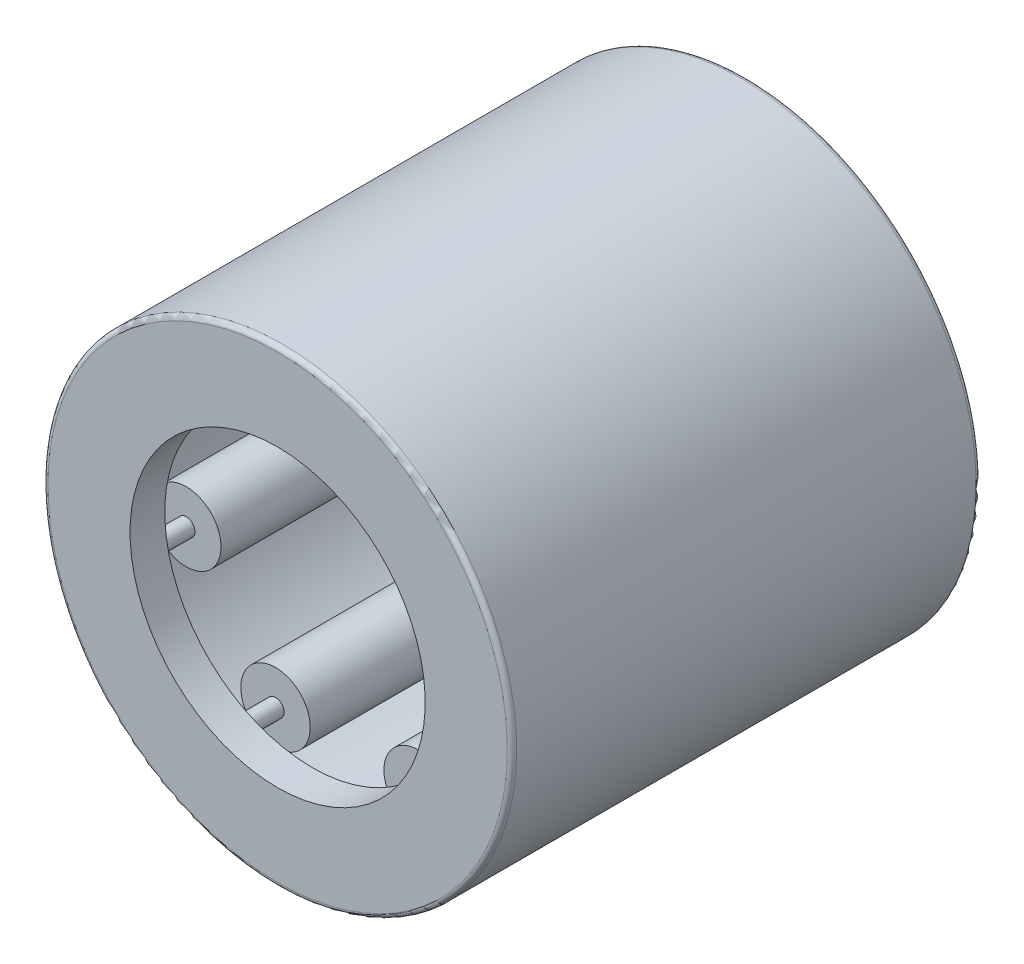
SolidWorks part; units mm, degrees
ref_plane "Front Plane" through (0, 0, 0) normal (0, 0, 1) x (1, 0, 0)
ref_plane "Top Plane" through (0, 0, 0) normal (0, 1, 0) x (1, 0, 0)
ref_plane "Right Plane" through (0, 0, 0) normal (1, 0, 0) x (0, 0, -1)
sketch "Sketch1" plane through (0, 0, 0) normal (1, 0, 0) x (0, 0, -1)
  line L0 (-4.5, 0) -> (4.5, 0) construction
  line L1 (0, 0) -> (0, 4.5) construction
  line L2 (-4.5, 0) -> (-4.5, 4.5) construction
  line L3 (-4.5, 4.5) -> (4.5, 4.5)
  line L4 (4.5, 4.5) -> (4.5, 0) construction
  line L5 (4.5, 0) -> (3.8333, 0) construction
  line L6 (3.8333, 0) -> (3.8333, 3.8333) construction
  line L7 (3.8333, 3.8333) -> (-3.8333, 3.8333)
  line L8 (-3.8333, 3.8333) -> (-3.8333, 0) construction
  line L9 (-3.8333, 0) -> (-4.5, 0) construction
  line L10 (-4.5, 4.5) -> (-4.5, 2.8333)
  line L11 (-4.5, 2.8333) -> (-3.8333, 2.8333)
  line L12 (-3.8333, 2.8333) -> (-3.8333, 3.8333)
  line L13 (3.8333, 4.5) -> (3.8333, 3.8333) construction
  line L14 (3.8333, 3.8333) -> (3.8333, 2.8333)
  line L15 (3.8333, 2.8333) -> (4.5, 2.8333)
  line L16 (4.5, 2.8333) -> (4.5, 4.5)
  line L17 (3.8333, 3.8333) -> (3.8333, 3.1667) construction
  line L18 (3.8333, 3.1667) -> (3.8333, 2.5) construction
  line L19 (3.8333, -3.8333) -> (3.8333, -3.1667) construction
  line L20 (3.8333, -4.5) -> (3.8333, -3.8333) construction
  line L21 (4.5, -2.8333) -> (4.5, -4.5) construction
  line L22 (3.8333, -2.8333) -> (4.5, -2.8333) construction
  line L23 (3.8333, -3.8333) -> (3.8333, -2.8333) construction
  line L24 (-3.8333, -2.8333) -> (-3.8333, -3.8333) construction
  line L25 (-4.5, -2.8333) -> (-3.8333, -2.8333) construction
  line L26 (-4.5, -4.5) -> (-4.5, -2.8333) construction
  line L27 (3.8333, -3.8333) -> (-3.8333, -3.8333) construction
  line L28 (-4.5, -4.5) -> (4.5, -4.5) construction
  point P4 (0, 2.5)
  dimension "Width" = 9
  dimension "Shaft Dia" = 5
  dimension "OD" = 9
sketch "Sketch7" plane through (0, 0, 0) normal (1, 0, 0) x (0, 0, -1)
  line L0 (-4.5, 4.5) -> (-4.5, 2.8333) construction
  line L1 (-4.5, 2.8333) -> (-3.8333, 2.8333) construction
  line L2 (-3.8333, 2.8333) -> (-3.8333, 3.8333) construction
  line L3 (3.8333, 3.8333) -> (-3.8333, 3.8333) construction
  line L4 (3.8333, 3.8333) -> (3.8333, 2.8333) construction
  line L5 (3.8333, 2.8333) -> (4.5, 2.8333) construction
  line L6 (4.5, 2.8333) -> (4.5, 4.5) construction
  line L8 (-4.5, 4.5) -> (4.5, 4.5) construction
  line L9 (-4.5, 4.5) -> (-4.5, 2.8333)
  line L10 (-4.5, 2.8333) -> (-3.8333, 2.8333)
  line L13 (-3.8333, 2.8333) -> (-3.8333, 3.8333)
  line L16 (3.8333, 3.8333) -> (-3.8333, 3.8333)
  line L17 (3.8333, 3.8333) -> (3.8333, 2.8333)
  line L18 (3.8333, 2.8333) -> (4.5, 2.8333)
  line L19 (4.5, 2.8333) -> (4.5, 4.5)
  line L20 (-4.5, 4.5) -> (4.5, 4.5)
revolve "Revolve1" add sketch "Sketch7" angle 360 about L0
sketch "Sketch2" plane through (0, 0, 0) normal (1, 0, 0) x (0, 0, -1)
  line L0 (-4.5, 2.8333) -> (-3.8333, 2.8333) construction
  line L1 (-3.1667, 3.1667) -> (3.1667, 3.1667) construction
  line L2 (-3.1667, 3.1667) -> (-3.1667, 3.8333) construction
  line L3 (-3.1667, 3.8333) -> (3.1667, 3.8333)
  line L4 (3.1667, 3.1667) -> (3.1667, 3.8333) construction
  line L5 (3.8333, 2.8333) -> (4.5, 2.8333) construction
  line L6 (-3.8333, 3.1667) -> (-3.1667, 3.1667) construction
  line L7 (3.1667, 3.1667) -> (3.8333, 3.1667) construction
  line L8 (4.5, 4.5) -> (4.5, 0) construction
  line L9 (-3.1667, 3.3333) -> (-3.1667, 3) construction
  line L10 (-3.8333, 3.1667) -> (-3.8333, 2.8333) construction
  line L11 (-3.1667, 3.8333) -> (-3.1667, 3.3333)
  line L12 (3.1667, 3.8333) -> (3.1667, 3.3333)
  line L13 (3.1667, 3.3333) -> (-3.1667, 3.3333)
  line L14 (0, 3.8333) -> (0, 2.5) construction
  line L16 (-3.1667, 3) -> (-3.8333, 3) construction
  line L17 (0, 0) -> (4.5, 0) construction
  line L18 (-3.1667, -3) -> (-3.8333, -3) construction
  line L19 (0, -3.8333) -> (0, -2.5) construction
  line L20 (-3.8333, -3.1667) -> (-3.8333, -2.8333) construction
  line L21 (-3.1667, -3.3333) -> (-3.1667, -3) construction
  line L22 (3.1667, -3.1667) -> (3.8333, -3.1667) construction
  line L23 (-3.8333, -3.1667) -> (-3.1667, -3.1667) construction
  line L24 (3.1667, -3.1667) -> (3.1667, -3.8333) construction
  line L25 (-3.1667, -3.1667) -> (-3.1667, -3.8333) construction
  line L26 (-3.1667, -3.1667) -> (3.1667, -3.1667) construction
  line L27 (3.1667, -3.3333) -> (-3.1667, -3.3333) construction
  line L28 (3.1667, -3.8333) -> (3.1667, -3.3333) construction
  line L29 (-3.1667, -3.8333) -> (-3.1667, -3.3333) construction
  line L30 (-3.1667, -3.8333) -> (3.1667, -3.8333) construction
  line L33 (3.8333, 3.8333) -> (-3.8333, 3.8333) construction
  line L34 (3.8333, 3.8333) -> (3.8333, 2.8333) construction
  line L35 (-3.8333, 2.8333) -> (-3.8333, 3.8333) construction
  line L36 (0, 0) -> (0, 4.5) construction
  point P16 (0, 3.1667)
revolve "Revolve2" add sketch "Sketch2" angle 360 about L1
sketch "Sketch3" plane through (0, 0, 0) normal (1, 0, 0) x (0, 0, -1)
  line L1 (-3.8333, 3.1667) -> (3.8333, 3.1667)
  line L2 (-3.8333, 3.1667) -> (-3.8333, 3.3333)
  line L3 (-3.8333, 3.3333) -> (3.8333, 3.3333)
  line L4 (3.8333, 3.1667) -> (3.8333, 3.3333)
  line L5 (0, 0) -> (4.5, 0) construction
  line L7 (3.8333, -3.1667) -> (3.8333, -3.3333) construction
  line L8 (-3.8333, -3.3333) -> (3.8333, -3.3333) construction
  line L9 (-3.8333, -3.1667) -> (-3.8333, -3.3333) construction
  line L10 (-3.8333, -3.1667) -> (3.8333, -3.1667) construction
  line L11 (3.8333, 3.8333) -> (3.8333, 2.8333) construction
  line L12 (4.5, 4.5) -> (4.5, 0) construction
revolve "Revolve3" add sketch "Sketch3" angle 360 about L1
ref_axis "Axis1" through (0, 2.8333, 4.5) along (0, 1, 0)
pattern_circular "CirPattern1" count 7 every 51.429 about axis through (0, 0, 4.5) along (0, 0, -1) of bodies 166 167
fillet "Fillet1" radius 0.09 2 edges at (0, -4.5, -4.5) (0, -4.5, 4.5)
sketch "Sketch4" plane through (0, 0, 0) normal (1, 0, 0) x (0, 0, -1)
  line L0 (3.1667, 3.8333) -> (3.1667, 3.3333) construction
  line L1 (4.41, 2.5) -> (3.1667, 2.5)
  line L2 (4.41, 2.5) -> (4.41, 2.8333)
  line L3 (4.41, 2.8333) -> (3.1667, 2.8333)
  line L4 (3.1667, 2.5) -> (3.1667, 2.8333)
  line L7 (3.8333, 2.8333) -> (4.5, 2.8333) construction
  line L8 (4.41, -4.5) -> (4.41, 4.5) construction
revolve "Revolve4" [suppressed] add sketch "Sketch4" angle 360 about L0
sketch "Sketch5" plane through (0, 0, 0) normal (1, 0, 0) x (0, 0, -1)
  line L0 (-4.41, 4.5) -> (-4.41, -4.5) construction
  line L1 (-3.1667, 2.5) -> (-4.41, 2.5)
  line L2 (-3.1667, 2.5) -> (-3.1667, 2.8333)
  line L3 (-3.1667, 2.8333) -> (-4.41, 2.8333)
  line L4 (-4.41, 2.5) -> (-4.41, 2.8333)
  line L5 (-3.1667, 3.8333) -> (-3.1667, 3.3333) construction
  line L6 (-4.5, 2.8333) -> (-3.8333, 2.8333) construction
revolve "Revolve5" [suppressed] add sketch "Sketch5" angle 360 about L0
sketch "Front View" plane through (0, 0, 0) normal (0, 0, 1) x (1, 0, 0)
  circle A0 centre (0, 0) radius 2.5 construction
  circle A1 centre (0, 0) radius 4.5 construction
  dimension "OD" = 9
  dimension "ID" = 5
sketch "Right View" plane through (0, 0, 0) normal (1, 0, 0) x (0, 0, -1)
  line L0 (-4.5, 4.5) -> (4.5, 4.5) construction
  line L1 (-4.5, 4.5) -> (4.5, 4.5) construction
  line L2 (0, 0) -> (0, 4.5) construction
  point P4 (0, 4.5)
  dimension "Width" = 9
equation "\"Rollers@CirPattern1\"=\"OD@Sketch1\"*.75"
equation "\"D1@Fillet1\" = \"OD@Sketch1\" * .01"
equation "\"Angle@CirPattern1\"= 360 / \"Rollers@CirPattern1\""
equation "\"ID@Front View\"= \"Shaft Dia@Sketch1\""
equation "\"OD@Front View\" = \"OD@Sketch1\""
equation "\"Width@Right View\"=\"Width@Sketch1\""
